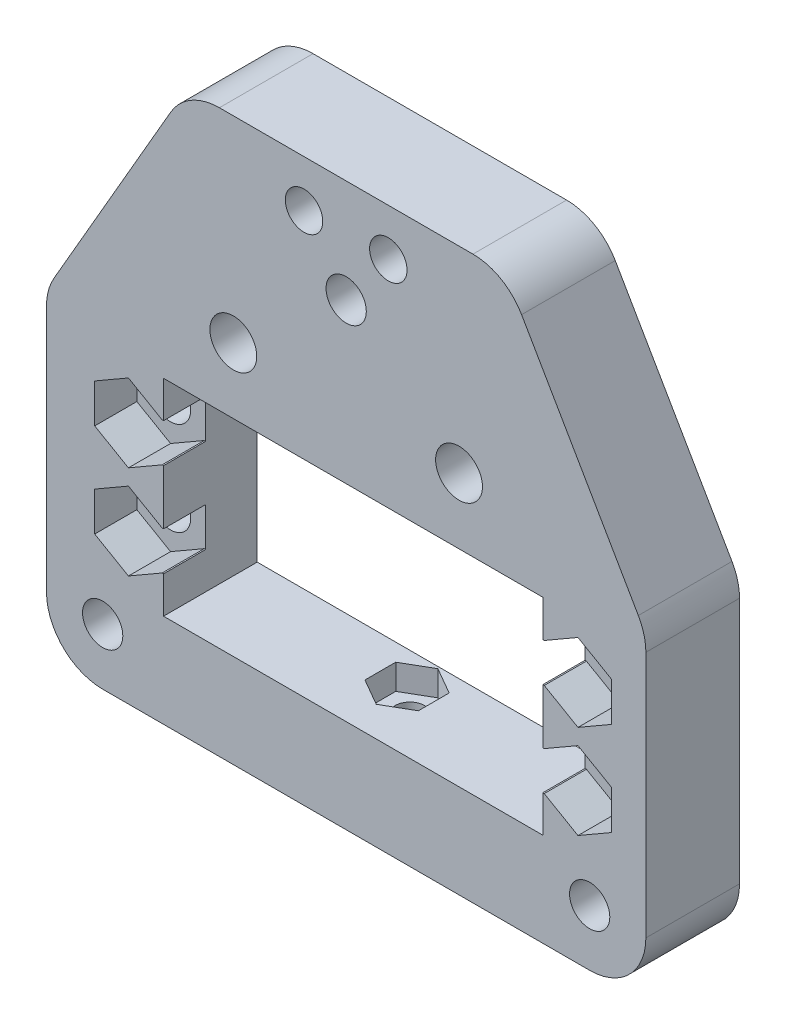
SolidWorks part; units mm, degrees
material "ABS"
ref_plane "Спереди" through (0, 0, 0) normal (0, 0, 1) x (1, 0, 0)
ref_plane "Сверху" through (0, 0, 0) normal (0, 1, 0) x (1, 0, 0)
ref_plane "Справа" through (0, 0, 0) normal (1, 0, 0) x (0, 0, -1)
sketch "Эскиз1" plane through (0, 0, 0) normal (0, 0, 1) x (1, 0, 0)
  line L0 (0, 0) -> (64, 0)
  line L1 (64, 0) -> (64, 34.0192)
  line L2 (64, 34.0192) -> (49, 60)
  line L3 (49, 60) -> (15, 60)
  line L4 (15, 60) -> (0, 34.02)
  line L5 (0, 34.02) -> (0, 0)
  dimension "D1" = 64
  dimension "D2" = 60
  dimension "D3" = 34
  dimension "D4" = 30
  dimension "D5" = 120
  dimension "D6" = 34.02
extrude "Бобышка-Вытянуть1" add sketch "Эскиз1" along normal blind 10 contours L0 L1 L2 L3 L4 L5
fillet "Скругление1" radius 6 6 edges at (49, 60, 5) (15, 60, 5) (0, 34.02, 5) (0, 0, 5) (64, 34.0192, 5) (64, 0, 5)
sketch "Эскиз2" plane through (0, 0, 10) normal (0, 0, 1) x (1, 0, 0)
  line L0 (12.5, 32) -> (53, 32)
  line L1 (53, 32) -> (53, 10)
  line L2 (53, 10) -> (12.5, 10)
  line L3 (12.5, 10) -> (12.5, 32)
  line L4 (64, 6) -> (64, 32.4115) construction
  line L5 (6, 0) -> (58, 0) construction
  dimension "D1" = 22
  dimension "D2" = 40.5
  dimension "D3" = 11
  dimension "D4" = 10
extrude "Вырез-Вытянуть1" cut sketch "Эскиз2" against normal through all
hole_wizard "Отверстия под штифты Ø4.0 мм1" positions "Эскиз3" profile "Эскиз4" hole size "Ø4.0" standard "Ansi Metric" end condition through all
sketch "Эскиз3" plane through (0, 0, 10) normal (0, 0, 1) x (1, 0, 0)
  line L0 (45.5359, 60) -> (18.4641, 60) construction
  line L1 (64, 6) -> (64, 32.4115) construction
  line L2 (32, 62.7032) -> (32, 49.5714) construction
  point P0 (27.4999, 55)
  point P2 (36.5, 55)
  point P13 (32, 60)
  dimension "D1" = 5
  dimension "D2" = 27.5
sketch "Эскиз4" plane through (27.4999, 55, 10) normal (1, 0, 0) x (0, -1, 0)
  line L0 (0, 0) -> (0, 10)
  line L1 (0, 10) -> (2, 10)
  line L2 (2, 10) -> (2, 0)
  line L5 (2, 0) -> (0, 0)
  line L11 (0, -6.35) -> (0, 13.871) construction
  dimension "Диаметр сквозного отверстия" = 4
  dimension "Глубина сквозного отверстия" = 10
hole_wizard "Отверстия под штифты Ø5.0 мм1" positions "Эскиз5" profile "Эскиз6" hole size "Ø5.0" standard "Ansi Metric" end condition through all
sketch "Эскиз5" plane through (0, 0, 10) normal (0, 0, 1) x (1, 0, 0)
  line L0 (45.5359, 60) -> (18.4641, 60) construction
  line L1 (64, 6) -> (64, 32.4115) construction
  line L2 (32, 62.5774) -> (32, 29.5493) construction
  point P0 (19.9499, 39)
  point P2 (44.05, 39)
  point P13 (32, 60)
  dimension "D1" = 21
  dimension "D2" = 19.95
sketch "Эскиз6" plane through (19.9499, 39, 10) normal (1, 0, 0) x (0, -1, 0)
  line L0 (0, 0) -> (0, 10)
  line L1 (0, 10) -> (2.5, 10)
  line L2 (2.5, 10) -> (2.5, 0)
  line L5 (2.5, 0) -> (0, 0)
  line L11 (0, -6.35) -> (0, 13.4589) construction
  dimension "Диаметр сквозного отверстия" = 5
  dimension "Глубина сквозного отверстия" = 10
hole_wizard "Сверло под метчик  спиральное M41" positions "Эскиз7" profile "Эскиз8" hole size "M4x0.7" standard "Ansi Metric" end condition through all
sketch "Эскиз7" plane through (0, 0, 10) normal (0, 0, 1) x (1, 0, 0)
  line L0 (53, 10) -> (53, 32) construction
  line L1 (53, 32) -> (12.5, 32) construction
  line L2 (32.75, 34.3929) -> (32.75, 8.0575) construction
  point P0 (56.75, 26)
  point P2 (56.75, 16)
  point P4 (8.75, 26)
  point P6 (8.75, 16)
  point P25 (32.75, 32)
  dimension "D1" = 3.75
  dimension "D2" = 6
  dimension "D3" = 10
sketch "Эскиз8" plane through (56.75, 26, 10) normal (1, 0, 0) x (0, -1, 0)
  line L0 (0, 0) -> (0, 10)
  line L1 (0, 10) -> (2.15, 10)
  line L2 (2.15, 10) -> (2.15, 0)
  line L5 (2.15, 0) -> (0, 0)
  line L11 (0, -6.35) -> (0, 14.6481) construction
  dimension "Диаметр сквозного отверстия" = 4.3
  dimension "Глубина сквозного отверстия" = 10
sketch "Эскиз9" plane through (0, 0, 10) normal (0, 0, -1) x (-1, 0, 0)
  line L0 (-56.75, 30.803) -> (-56.75, 10.8409) construction
  line L1 (-56.75, 30.1569) -> (-60.35, 28.0785)
  line L2 (-60.35, 28.0785) -> (-60.35, 23.9215)
  line L3 (-60.35, 23.9215) -> (-56.75, 21.8431)
  line L4 (-56.75, 21.8431) -> (-53.15, 23.9215)
  line L5 (-53.15, 23.9215) -> (-53.15, 28.0785)
  line L6 (-53.15, 28.0785) -> (-56.75, 30.1569)
  line L7 (-56.75, 20.1569) -> (-60.35, 18.0785)
  line L8 (-60.35, 18.0785) -> (-60.35, 13.9215)
  line L9 (-60.35, 13.9215) -> (-56.75, 11.8431)
  line L10 (-56.75, 11.8431) -> (-53.15, 13.9215)
  line L11 (-53.15, 13.9215) -> (-53.15, 18.0785)
  line L12 (-53.15, 18.0785) -> (-56.75, 20.1569)
  line L13 (-8.75, 30.1569) -> (-12.35, 28.0785)
  line L14 (-12.35, 28.0785) -> (-12.35, 23.9215)
  line L15 (-12.35, 23.9215) -> (-8.75, 21.8431)
  line L16 (-8.75, 21.8431) -> (-5.15, 23.9215)
  line L17 (-5.15, 23.9215) -> (-5.15, 28.0785)
  line L18 (-5.15, 28.0785) -> (-8.75, 30.1569)
  line L19 (-8.75, 20.1569) -> (-12.35, 18.0785)
  line L20 (-12.35, 18.0785) -> (-12.35, 13.9215)
  line L21 (-12.35, 13.9215) -> (-8.75, 11.8431)
  line L22 (-8.75, 11.8431) -> (-5.15, 13.9215)
  line L23 (-5.15, 13.9215) -> (-5.15, 18.0785)
  line L24 (-5.15, 18.0785) -> (-8.75, 20.1569)
  line L25 (-8.75, 30.803) -> (-8.75, 11.1079) construction
  circle A0 centre (-56.75, 26) radius 3.6 construction
  circle A1 centre (-56.75, 16) radius 3.6 construction
  circle A2 centre (-8.75, 26) radius 3.6 construction
  circle A3 centre (-8.75, 16) radius 3.6 construction
  dimension "D1" = 7.2
  dimension "D2" = 7.2
  dimension "D3" = 7.2
  dimension "D4" = 7.2
  dimension "D5" = 60
  dimension "D6" = 60
  dimension "D7" = 60
  dimension "D8" = 60
extrude "Вырез-Вытянуть4" cut sketch "Эскиз9" along normal blind 4.5
sketch "Эскиз12" plane through (0, 10, 0) normal (0, 1, 0) x (1, 0, 0)
  line L0 (32, 0.39) -> (32, -7.3916) construction
  line L1 (32, -0.2091) -> (29.15, -1.8546)
  line L2 (29.15, -1.8546) -> (29.15, -5.1454)
  line L3 (29.15, -5.1454) -> (32, -6.7909)
  line L4 (32, -6.7909) -> (34.85, -5.1454)
  line L5 (34.85, -5.1454) -> (34.85, -1.8546)
  line L6 (34.85, -1.8546) -> (32, -0.2091)
  line L7 (45.5359, 0) -> (18.4641, 0) construction
  circle A0 centre (32, -3.5) radius 2.85 construction
  point P12 (32, 0)
  dimension "D1" = 5.7
  dimension "D2" = 60
  dimension "D3" = 3.5
extrude "Вырез-Вытянуть6" cut sketch "Эскиз12" against normal blind 2.7 contours L3 L4 L5 L6 L1 L2
hole_wizard "Сверло под метчик  спиральное M32" positions "Эскиз13" profile "Эскиз14" hole size "M3x0.5" standard "Ansi Metric"
sketch "Эскиз13" plane through (0, 0, 0) normal (0, -1, 0) x (-1, 0, 0)
  line L0 (-6, 0) -> (-58, 0) construction
  line L1 (-64, -10) -> (-64, 0) construction
  point P0 (-32, -3.2)
  dimension "D1" = 3.2
  dimension "D2" = 32
sketch "Эскиз14" plane through (32, 0, 3.2) normal (1, 0, 0) x (0, 0, -1)
  line L0 (0, 0) -> (0, 10.9464)
  line L1 (0, 10.9464) -> (1.575, 10)
  line L2 (1.575, 10) -> (1.575, 0)
  line L5 (1.575, 0) -> (0, 0)
  line L10 (0, 10.9464) -> (-1.575, 10) construction
  line L11 (0, -6.35) -> (0, 107.95) construction
  dimension "Диаметр отверстия" = 3.15
  dimension "Глубина отверстия" = 10
  dimension "Угол заточки сверла" = 118
hole_wizard "Сверло под метчик  спиральное M42" positions "Эскиз16" profile "Эскиз17" hole size "M4x0.7" standard "Ansi Metric" end condition through all
sketch "Эскиз16" plane through (0, 0, 10) normal (0, 0, 1) x (1, 0, 0)
  line L0 (45.5359, 60) -> (18.4641, 60) construction
  line L1 (64, 6) -> (64, 32.4115) construction
  line L2 (6, 0) -> (58, 0) construction
  line L3 (32, -2.539) -> (32, 12.8188) construction
  point P0 (32, 49)
  point P2 (6, 6)
  point P4 (58, 6)
  point P19 (32, 0)
  dimension "D1" = 11
  dimension "D2" = 32
  dimension "D3" = 6
  dimension "D4" = 6
sketch "Эскиз17" plane through (32, 49, 10) normal (1, 0, 0) x (0, -1, 0)
  line L0 (0, 0) -> (0, 10)
  line L1 (0, 10) -> (2.15, 10)
  line L2 (2.15, 10) -> (2.15, 0)
  line L5 (2.15, 0) -> (0, 0)
  line L11 (0, -6.35) -> (0, 15.6845) construction
  dimension "Диаметр сквозного отверстия" = 4.3
  dimension "Глубина сквозного отверстия" = 10
sketch "Эскиз18" plane through (0, 0, 0) normal (0, 0, -1) x (-1, 0, 0)
  line L0 (-32, 53.874) -> (-32, 44.3135) construction
  line L1 (-32, 53.1569) -> (-35.6, 51.0785)
  line L2 (-35.6, 51.0785) -> (-35.6, 46.9215)
  line L3 (-35.6, 46.9215) -> (-32, 44.8431)
  line L4 (-32, 44.8431) -> (-28.4, 46.9215)
  line L5 (-28.4, 46.9215) -> (-28.4, 51.0785)
  line L6 (-28.4, 51.0785) -> (-32, 53.1569)
  line L7 (-58, 10.1569) -> (-61.6, 8.0785)
  line L8 (-61.6, 8.0785) -> (-61.6, 3.9215)
  line L9 (-61.6, 3.9215) -> (-58, 1.8431)
  line L10 (-58, 1.8431) -> (-54.4, 3.9215)
  line L11 (-54.4, 3.9215) -> (-54.4, 8.0785)
  line L12 (-54.4, 8.0785) -> (-58, 10.1569)
  line L13 (-6, 10.1569) -> (-9.6, 8.0785)
  line L14 (-9.6, 8.0785) -> (-9.6, 3.9215)
  line L15 (-9.6, 3.9215) -> (-6, 1.8431)
  line L16 (-6, 1.8431) -> (-2.4, 3.9215)
  line L17 (-2.4, 3.9215) -> (-2.4, 8.0785)
  line L18 (-2.4, 8.0785) -> (-6, 10.1569)
  line L19 (-58, 11.3834) -> (-58, 0.9026) construction
  line L20 (-6, 11.3834) -> (-6, 0.9026) construction
  circle A0 centre (-32, 49) radius 3.6 construction
  circle A1 centre (-58, 6) radius 3.6 construction
  circle A2 centre (-6, 6) radius 3.6 construction
  dimension "D1" = 7.2
  dimension "D2" = 7.2
  dimension "D3" = 7.2
  dimension "D4" = 60
  dimension "D5" = 60
  dimension "D6" = 60
extrude "Вырез-Вытянуть7" cut sketch "Эскиз18" against normal blind 3.2
sketch "Эскиз19" plane through (53, 0, 0) normal (-1, 0, 0) x (0, 0, 1)
  line L0 (10, 28.0785) -> (5.5, 28.0785)
  line L1 (10, 10) -> (10, 32) construction
  line L2 (5.5, 28.0785) -> (5.5, 23.9215)
  line L3 (5.5, 23.9215) -> (10, 23.9215)
  line L4 (10, 23.9215) -> (10, 28.0785)
  dimension "D1" = 4.5
extrude "Вырез-Вытянуть13" cut sketch "Эскиз19" against normal blind 0.15 contours L3 L4 L0 L2
sketch "Эскиз21" plane through (12.5, 0, 0) normal (1, 0, 0) x (0, 0, -1)
  line L0 (-10, 28.0785) -> (-5.5, 28.0785)
  line L1 (-10, 32) -> (-10, 10) construction
  line L2 (-5.5, 28.0785) -> (-5.5, 23.9215)
  line L3 (-5.5, 23.9215) -> (-10, 23.9215)
  line L4 (-10, 23.9215) -> (-10, 28.0785)
  dimension "D1" = 4.5
extrude "Вырез-Вытянуть14" cut sketch "Эскиз21" against normal blind 0.15
sketch "Эскиз22" plane through (53, 0, 0) normal (-1, 0, 0) x (0, 0, 1)
  line L0 (10, 18.0785) -> (5.5, 18.0785)
  line L1 (10, 10) -> (10, 23.9215) construction
  line L2 (5.5, 18.0785) -> (5.5, 13.9215)
  line L3 (5.5, 13.9215) -> (10, 13.9215)
  line L4 (10, 13.9215) -> (10, 18.0785)
  dimension "D1" = 4.5
extrude "Вырез-Вытянуть15" cut sketch "Эскиз22" against normal blind 0.15
sketch "Эскиз23" plane through (12.5, 0, 0) normal (1, 0, 0) x (0, 0, -1)
  line L0 (-10, 18.0785) -> (-5.5, 18.0785)
  line L1 (-10, 23.9215) -> (-10, 10) construction
  line L2 (-5.5, 18.0785) -> (-5.5, 13.9215)
  line L3 (-5.5, 13.9215) -> (-10, 13.9215)
  line L4 (-10, 13.9215) -> (-10, 18.0785)
  dimension "D1" = 4.5
extrude "Вырез-Вытянуть16" cut sketch "Эскиз23" against normal blind 0.15
